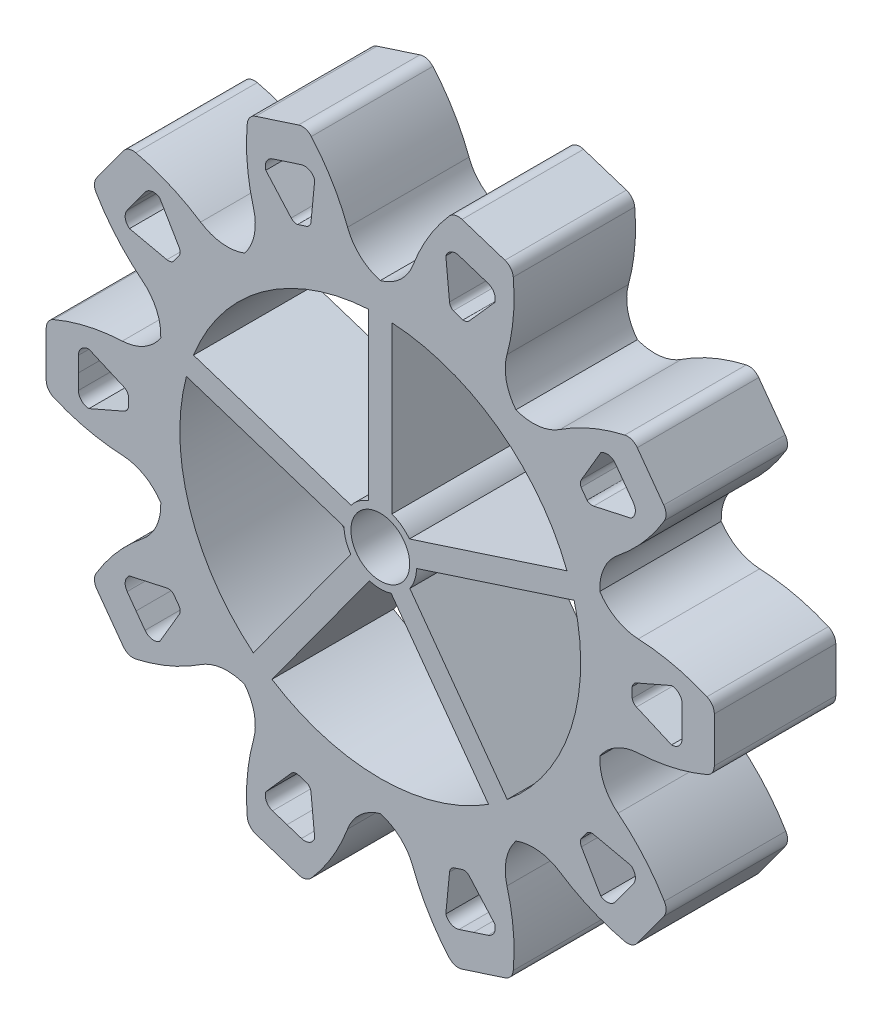
SolidWorks part; units mm, degrees
ref_plane "Front Plane" through (0, 0, 0) normal (0, 0, 1) x (1, 0, 0)
ref_plane "Top Plane" through (0, 0, 0) normal (0, 1, 0) x (1, 0, 0)
ref_plane "Right Plane" through (0, 0, 0) normal (1, 0, 0) x (0, 0, -1)
sketch "Sketch1" plane through (0, 0, 0) normal (0, 0, 1) x (1, 0, 0)
  line L0 (-4.8253, 83.681) -> (-4.8253, 14.3756)
  line L1 (4.8253, 83.681) -> (4.8253, 14.3756)
  line L2 (78.0943, 30.448) -> (12.1809, 9.0314)
  line L3 (81.0765, 21.2697) -> (15.1631, -0.1468)
  line L4 (53.0902, -64.8631) -> (12.3535, -8.7938)
  line L5 (45.2827, -70.5356) -> (4.546, -14.4663)
  line L6 (-45.2827, -70.5356) -> (-4.546, -14.4663)
  line L7 (-53.0902, -64.8631) -> (-12.3535, -8.7938)
  line L8 (-81.0765, 21.2697) -> (-15.1631, -0.1468)
  line L9 (-78.0943, 30.448) -> (-12.1809, 9.0314)
  line L10 (0, 0) -> (0, 264.1098) construction
  line L11 (0, 0) -> (-74.7246, 229.9787) construction
  line L12 (-69.1627, 110.1483) -> (-9.6173, 129.4958) construction
  line L13 (-55.2481, 128.9381) -> (-31.0913, 136.7871)
  line L14 (31.0913, 136.7871) -> (55.2481, 128.9381)
  line L15 (105.5548, 92.3881) -> (120.4845, 71.8391)
  line L16 (139.7, 12.7) -> (139.7, -12.7)
  line L17 (120.4845, -71.8391) -> (105.5548, -92.3881)
  line L18 (55.2481, -128.9381) -> (31.0913, -136.7871)
  line L19 (-31.0913, -136.7871) -> (-55.2481, -128.9381)
  line L20 (-105.5548, -92.3881) -> (-120.4845, -71.8391)
  line L21 (-139.7, -12.7) -> (-139.7, 12.7)
  line L22 (-120.4845, 71.8391) -> (-105.5548, 92.3881)
  circle A0 centre (0, 0) radius 83.82
  circle A1 centre (0, 0) radius 96.52
  arc A2 (-9.0459, 8.3101) -> (9.2099, 8.128) centre (0, 0) ccw construction
  arc A3 (-4.8253, 14.3756) -> (-12.1809, 9.0314) centre (0, 0) ccw
  arc A4 (-15.1631, -0.1468) -> (-12.3535, -8.7938) centre (0, 0) ccw
  arc A5 (-4.546, -14.4663) -> (4.546, -14.4663) centre (0, 0) ccw
  arc A6 (12.3535, -8.7938) -> (15.1631, -0.1468) centre (0, 0) ccw
  arc A7 (12.1809, 9.0314) -> (4.8253, 14.3756) centre (0, 0) ccw
  circle A8 centre (0, 0) radius 12.2836
  arc A9 (-31.0913, 136.7871) -> (-13.6811, 108.9903) centre (-91.3913, 79.6684) cw
  arc A10 (-13.6811, 108.9903) -> (0, 96.52) centre (5.408, 116.193) ccw
  arc A11 (-52.9946, 96.2165) -> (-56.733, 78.0863) centre (-72.6717, 90.8234) cw
  arc A12 (-55.2481, 128.9381) -> (-52.9946, 96.2165) centre (27.1092, 118.1716) ccw
  arc A13 (31.0913, 136.7871) -> (13.6811, 108.9903) centre (91.3913, 79.6684) ccw
  arc A14 (13.6811, 108.9903) -> (0, 96.52) centre (-5.408, 116.193) cw
  arc A15 (52.9946, 96.2165) -> (56.733, 78.0863) centre (72.6717, 90.8234) ccw
  arc A16 (55.2481, 128.9381) -> (52.9946, 96.2165) centre (-27.1092, 118.1716) cw
  arc A17 (105.5548, 92.3881) -> (75.1311, 80.1334) centre (120.765, 10.7347) ccw
  arc A18 (75.1311, 80.1334) -> (56.733, 78.0863) centre (63.9214, 97.1809) cw
  arc A19 (99.4282, 46.6914) -> (91.796, 29.8263) centre (112.1773, 30.7623) ccw
  arc A20 (120.4845, 71.8391) -> (99.4282, 46.6914) centre (47.5277, 111.5372) cw
  arc A21 (139.7, 12.7) -> (107.8836, 20.6683) centre (104.0106, -62.2994) ccw
  arc A22 (107.8836, 20.6683) -> (91.796, 29.8263) centre (108.835, 41.0489) cw
  arc A23 (107.8836, -20.6683) -> (91.796, -29.8263) centre (108.835, -41.0489) ccw
  arc A24 (139.7, -12.7) -> (107.8836, -20.6683) centre (104.0106, 62.2994) cw
  arc A25 (120.4845, -71.8391) -> (99.4282, -46.6914) centre (47.5277, -111.5372) ccw
  arc A26 (99.4282, -46.6914) -> (91.796, -29.8263) centre (112.1773, -30.7623) cw
  arc A27 (75.1311, -80.1334) -> (56.733, -78.0863) centre (63.9214, -97.1809) ccw
  arc A28 (105.5548, -92.3881) -> (75.1311, -80.1334) centre (120.765, -10.7347) cw
  arc A29 (55.2481, -128.9381) -> (52.9946, -96.2165) centre (-27.1092, -118.1716) ccw
  arc A30 (52.9946, -96.2165) -> (56.733, -78.0863) centre (72.6717, -90.8234) cw
  arc A31 (13.6811, -108.9903) -> (0, -96.52) centre (-5.408, -116.193) ccw
  arc A32 (31.0913, -136.7871) -> (13.6811, -108.9903) centre (91.3913, -79.6684) cw
  arc A33 (-31.0913, -136.7871) -> (-13.6811, -108.9903) centre (-91.3913, -79.6684) ccw
  arc A34 (-13.6811, -108.9903) -> (0, -96.52) centre (5.408, -116.193) cw
  arc A35 (-52.9946, -96.2165) -> (-56.733, -78.0863) centre (-72.6717, -90.8234) ccw
  arc A36 (-55.2481, -128.9381) -> (-52.9946, -96.2165) centre (27.1092, -118.1716) cw
  arc A37 (-105.5548, -92.3881) -> (-75.1311, -80.1334) centre (-120.765, -10.7347) ccw
  arc A38 (-75.1311, -80.1334) -> (-56.733, -78.0863) centre (-63.9214, -97.1809) cw
  arc A39 (-99.4282, -46.6914) -> (-91.796, -29.8263) centre (-112.1773, -30.7623) ccw
  arc A40 (-120.4845, -71.8391) -> (-99.4282, -46.6914) centre (-47.5277, -111.5372) cw
  arc A41 (-139.7, -12.7) -> (-107.8836, -20.6683) centre (-104.0106, 62.2994) ccw
  arc A42 (-107.8836, -20.6683) -> (-91.796, -29.8263) centre (-108.835, -41.0489) cw
  arc A43 (-107.8836, 20.6683) -> (-91.796, 29.8263) centre (-108.835, 41.0489) ccw
  arc A44 (-139.7, 12.7) -> (-107.8836, 20.6683) centre (-104.0106, -62.2994) cw
  arc A45 (-120.4845, 71.8391) -> (-99.4282, 46.6914) centre (-47.5277, 111.5372) ccw
  arc A46 (-99.4282, 46.6914) -> (-91.796, 29.8263) centre (-112.1773, 30.7623) cw
  arc A47 (-75.1311, 80.1334) -> (-56.733, 78.0863) centre (-63.9214, 97.1809) ccw
  arc A48 (-105.5548, 92.3881) -> (-75.1311, 80.1334) centre (-120.765, 10.7347) cw
  point P29 (0, 0)
  point P50 (-43.1697, 132.8626)
  point P135 (0, 0)
  dimension "D2" = 193.04
  dimension "D6" = 12.7
  dimension "D3" = 18
  dimension "D4" = 90
  dimension "D5" = 139.7
  dimension "D8" = 25.4
  dimension "D1" = 5
  dimension "D7" = 10
extrude "Boss-Extrude1" add sketch "Sketch1" along normal blind 50.8 contours L2 A7 L1 A0 L0 A3 L9 L8 A4 L7 L6 A5 L5 L4 A6 L3 A8 | A1 A0 | A16 L14 A13 A14 A1 A15 | A20 L15 A17 A18 A1 A19 | L13 A12 A11 A1 A10 A9 | A48 L22 A45 A46 A1 A47 | A44 L21 A41 A42 A1 A43 | A40 L20 A37 A38 A1 A39 | A36 L19 A33 A34 A1 A35 | A32 L18 A29 A30 A1 A31 | A28 L17 A25 A26 A1 A27 | A24 L16 A21 A22 A1 A23 region at (0, 81.5813, 0) region at (-35.6839, 109.8236, 0) region at (-28.9827, 89.1996, 0) region at (-93.4216, 67.8747, 0) region at (35.6839, 109.8236, 0) region at (-115.4754, 0, 0) region at (93.4216, 67.8747, 0) region at (-93.4216, -67.8747, 0) region at (115.4754, 0, 0) region at (-35.6839, -109.8236, 0) region at (35.6839, -109.8236, 0) region at (93.4216, -67.8747, 0)
fillet "Fillet1" radius 5.08 20 edges at (-31.0913, 136.7871, 25.4) (-55.2481, 128.9381, 25.4) (-105.5548, 92.3881, 25.4) (-120.4845, 71.8391, 25.4) (-139.7, 12.7, 25.4) (-139.7, -12.7, 25.4) (-120.4845, -71.8391, 25.4) (-105.5548, -92.3881, 25.4) (-55.2481, -128.9381, 25.4) (-31.0913, -136.7871, 25.4) (31.0913, -136.7871, 25.4) (55.2481, -128.9381, 25.4) (105.5548, -92.3881, 25.4) (120.4845, -71.8391, 25.4) (139.7, -12.7, 25.4) (139.7, 12.7, 25.4) (120.4845, 71.8391, 25.4) (105.5548, 92.3881, 25.4) (55.2481, 128.9381, 25.4) (31.0913, 136.7871, 25.4)
ref_axis "Axis1" through (0, 0, 50.8) along (0, 0, -1)
sketch "Sketch2" plane through (0, 0, 50.8) normal (0, 0, 1) x (1, 0, 0)
  line L0 (0, 0) -> (50.0065, 153.9041) construction
  line L1 (34.2109, 135.7735) -> (52.1284, 129.9517) construction
  line L2 (32.9488, 122.0046) -> (45.0594, 118.0798)
  line L3 (27.415, 119.1797) -> (28.9675, 103.2567)
  line L4 (30.5372, 100.85) -> (34.5731, 99.5387)
  line L5 (45.0564, 118.0706) -> (32.9518, 122.0138)
  line L6 (47.8728, 112.5325) -> (37.2575, 100.5631)
  line L7 (98.3686, 79.337) -> (105.8594, 69.0433)
  line L8 (104.8749, 62.9018) -> (89.2515, 59.4579)
  line L9 (92.2313, 80.3042) -> (84.128, 66.5098)
  line L10 (83.9833, 63.6401) -> (86.4776, 60.207)
  line L11 (126.215, 6.3654) -> (126.2247, -6.3654)
  line L12 (121.8183, -10.7553) -> (107.1545, -4.3583)
  line L13 (121.8183, 10.7553) -> (107.1545, 4.3583)
  line L14 (105.3506, 2.1218) -> (105.3506, -2.1218)
  line L15 (105.8515, -69.0376) -> (98.3765, -79.3427)
  line L16 (92.2313, -80.3042) -> (84.128, -66.5098)
  line L17 (104.8749, -62.9018) -> (89.2515, -59.4579)
  line L18 (86.4776, -60.207) -> (83.9833, -63.6401)
  line L19 (45.0564, -118.0706) -> (32.9518, -122.0138)
  line L20 (27.415, -119.1797) -> (28.9675, -103.2567)
  line L21 (47.8728, -112.5325) -> (37.2575, -100.5631)
  line L22 (34.5731, -99.5387) -> (30.5372, -100.85)
  line L23 (-32.9488, -122.0046) -> (-45.0594, -118.0798)
  line L24 (-47.8728, -112.5325) -> (-37.2575, -100.5631)
  line L25 (-27.415, -119.1797) -> (-28.9675, -103.2567)
  line L26 (-30.5372, -100.85) -> (-34.5731, -99.5387)
  line L27 (-98.3686, -79.337) -> (-105.8594, -69.0433)
  line L28 (-104.8749, -62.9018) -> (-89.2515, -59.4579)
  line L29 (-92.2313, -80.3042) -> (-84.128, -66.5098)
  line L30 (-83.9833, -63.6401) -> (-86.4776, -60.207)
  line L31 (-126.215, -6.3654) -> (-126.2247, 6.3654)
  line L32 (-121.8183, 10.7553) -> (-107.1545, 4.3583)
  line L33 (-121.8183, -10.7553) -> (-107.1545, -4.3583)
  line L34 (-105.3506, -2.1218) -> (-105.3506, 2.1218)
  line L35 (-105.8515, 69.0376) -> (-98.3765, 79.3427)
  line L36 (-92.2313, 80.3042) -> (-84.128, 66.5098)
  line L37 (-104.8749, 62.9018) -> (-89.2515, 59.4579)
  line L38 (-86.4776, 60.207) -> (-83.9833, 63.6401)
  line L39 (-45.0564, 118.0706) -> (-32.9518, 122.0138)
  line L40 (-27.415, 119.1797) -> (-28.9675, 103.2567)
  line L41 (-47.8728, 112.5325) -> (-37.2575, 100.5631)
  line L42 (-34.5731, 99.5387) -> (-30.5372, 100.85)
  arc A0 (32.9488, 122.0046) -> (27.415, 119.1797) centre (31.5943, 117.8253) ccw
  arc A1 (28.9675, 103.2567) -> (30.5372, 100.85) centre (32.0597, 103.5582) ccw
  arc A2 (37.2575, 100.5631) -> (34.5731, 99.5387) centre (34.9332, 102.6246) cw
  arc A3 (45.0564, 118.0706) -> (47.8728, 112.5325) centre (43.6956, 113.8933) cw
  arc A4 (105.8515, 69.0376) -> (104.8749, 62.9018) centre (102.2953, 66.458) cw
  arc A5 (89.2515, 59.4579) -> (86.4776, 60.207) centre (88.5827, 62.4918) cw
  arc A6 (84.128, 66.5098) -> (83.9833, 63.6401) centre (86.8068, 64.9361) ccw
  arc A7 (98.3686, 79.337) -> (92.2313, 80.3042) centre (94.8163, 76.752) ccw
  arc A8 (126.215, -6.3654) -> (121.8183, -10.7553) centre (121.8217, -6.362) cw
  arc A9 (107.1545, -4.3583) -> (105.3506, -2.1218) centre (108.3967, -1.5107) cw
  arc A10 (107.1545, 4.3583) -> (105.3506, 2.1218) centre (108.3967, 1.5107) ccw
  arc A11 (126.215, 6.3654) -> (121.8183, 10.7553) centre (121.8217, 6.362) ccw
  arc A12 (98.3686, -79.337) -> (92.2313, -80.3042) centre (94.8163, -76.752) cw
  arc A13 (84.128, -66.5098) -> (83.9833, -63.6401) centre (86.8068, -64.9361) cw
  arc A14 (89.2515, -59.4579) -> (86.4776, -60.207) centre (88.5827, -62.4918) ccw
  arc A15 (105.8515, -69.0376) -> (104.8749, -62.9018) centre (102.2953, -66.458) ccw
  arc A16 (32.9488, -122.0046) -> (27.415, -119.1797) centre (31.5943, -117.8253) cw
  arc A17 (28.9675, -103.2567) -> (30.5372, -100.85) centre (32.0597, -103.5582) cw
  arc A18 (37.2575, -100.5631) -> (34.5731, -99.5387) centre (34.9332, -102.6246) ccw
  arc A19 (45.0564, -118.0706) -> (47.8728, -112.5325) centre (43.6956, -113.8933) ccw
  arc A20 (-45.0564, -118.0706) -> (-47.8728, -112.5325) centre (-43.6956, -113.8933) cw
  arc A21 (-37.2575, -100.5631) -> (-34.5731, -99.5387) centre (-34.9332, -102.6246) cw
  arc A22 (-28.9675, -103.2567) -> (-30.5372, -100.85) centre (-32.0597, -103.5582) ccw
  arc A23 (-32.9488, -122.0046) -> (-27.415, -119.1797) centre (-31.5943, -117.8253) ccw
  arc A24 (-105.8515, -69.0376) -> (-104.8749, -62.9018) centre (-102.2953, -66.458) cw
  arc A25 (-89.2515, -59.4579) -> (-86.4776, -60.207) centre (-88.5827, -62.4918) cw
  arc A26 (-84.128, -66.5098) -> (-83.9833, -63.6401) centre (-86.8068, -64.9361) ccw
  arc A27 (-98.3686, -79.337) -> (-92.2313, -80.3042) centre (-94.8163, -76.752) ccw
  arc A28 (-126.215, 6.3654) -> (-121.8183, 10.7553) centre (-121.8217, 6.362) cw
  arc A29 (-107.1545, 4.3583) -> (-105.3506, 2.1218) centre (-108.3967, 1.5107) cw
  arc A30 (-107.1545, -4.3583) -> (-105.3506, -2.1218) centre (-108.3967, -1.5107) ccw
  arc A31 (-126.215, -6.3654) -> (-121.8183, -10.7553) centre (-121.8217, -6.362) ccw
  arc A32 (-98.3686, 79.337) -> (-92.2313, 80.3042) centre (-94.8163, 76.752) cw
  arc A33 (-84.128, 66.5098) -> (-83.9833, 63.6401) centre (-86.8068, 64.9361) cw
  arc A34 (-89.2515, 59.4579) -> (-86.4776, 60.207) centre (-88.5827, 62.4918) ccw
  arc A35 (-105.8515, 69.0376) -> (-104.8749, 62.9018) centre (-102.2953, 66.458) ccw
  arc A36 (-32.9488, 122.0046) -> (-27.415, 119.1797) centre (-31.5943, 117.8253) cw
  arc A37 (-28.9675, 103.2567) -> (-30.5372, 100.85) centre (-32.0597, 103.5582) cw
  arc A38 (-37.2575, 100.5631) -> (-34.5731, 99.5387) centre (-34.9332, 102.6246) ccw
  arc A39 (-45.0564, 118.0706) -> (-47.8728, 112.5325) centre (-43.6956, 113.8933) ccw
  point P5 (43.1697, 132.8626)
  point P8 (39.0041, 120.0422)
  point P18 (32.5551, 100.1944)
  point P22 (0, 0)
  point P23 (0, 0)
  point P35 (85.2304, 61.9235)
  point P49 (105.3506, 0)
  point P63 (85.2304, -61.9235)
  point P77 (32.5551, -100.1944)
  point P91 (-32.5551, -100.1944)
  point P105 (-85.2304, -61.9235)
  point P119 (-105.3506, 0)
  point P133 (-85.2304, 61.9235)
  point P147 (-32.5551, 100.1944)
  point P151 (0, 0)
  dimension "D1" = 10
extrude "Cut-Extrude1" cut sketch "Sketch2" against normal up to surface (50.8 mm away) contours L0 L4 A2 L6 A3 L5 | L4 L0 L2 A0 L3 A1 region at (32.3107, 112.944, 50.8) region at (40.2469, 110.3654, 50.8) up to face at (0, 0, 0)
pattern_circular "CirPattern1" count 10 over 360 about axis through (0, 0, 50.8) along (0, 0, -1) of "Cut-Extrude1"
